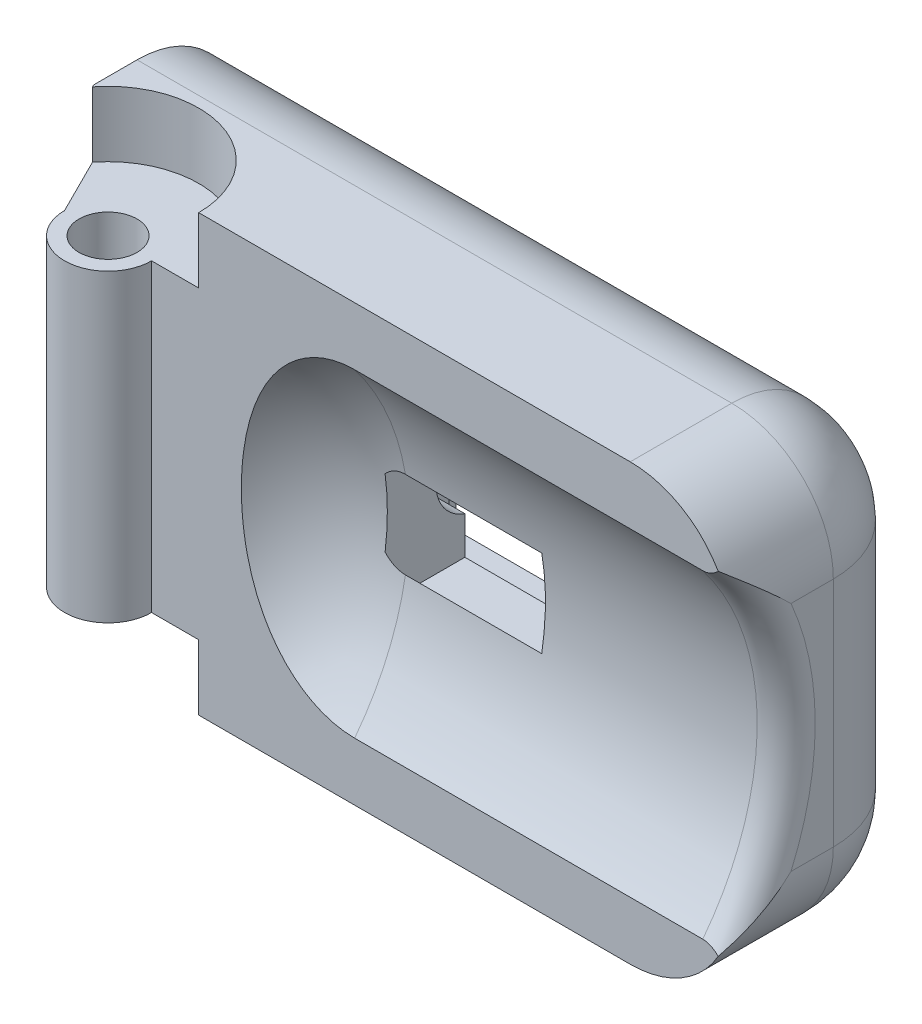
SolidWorks part; units mm, degrees
ref_plane "Alzado" through (0, 0, 0) normal (0, 0, 1) x (1, 0, 0)
ref_plane "Planta" through (0, 0, 0) normal (0, 1, 0) x (1, 0, 0)
ref_plane "Vista lateral" through (0, 0, 0) normal (1, 0, 0) x (0, 0, -1)
sketch "Croquis1" plane through (0, 0, 0) normal (0, 0, 1) x (1, 0, 0)
  line L1 (-43.9768, 15.9874) -> (4.0232, 15.9874)
  line L2 (-43.9768, 15.9874) -> (-43.9768, -14.0126)
  line L3 (-43.9768, -14.0126) -> (4.0232, -14.0126)
  line L4 (4.0232, 15.9874) -> (4.0232, -14.0126)
  dimension "D1" = 48
  dimension "D2" = 30
extrude "Saliente-Extruir1" add sketch "Croquis1" along normal blind 14
sketch "Croquis2" plane through (4.0232, 0, 0) normal (1, 0, 0) x (0, 0, -1)
  line L0 (-14, 15.9874) -> (-14, 11.9874) construction
  line L1 (-14, -14.0126) -> (-14, 15.9874) construction
  line L2 (-14, -14.0126) -> (-14, -10.0126) construction
  line L3 (-14, -14.0126) -> (0, -14.0126) construction
  line L4 (-14, 15.9874) -> (0, 15.9874) construction
  line L5 (-14, 0.9874) -> (-42.4956, 0.9874) construction
  line L6 (-14, 11.9874) -> (-14, -10.0126)
  arc A0 (-14, 11.9874) -> (-14, -10.0126) centre (-28.2478, 0.9874) cw
  line M3 (-14, 15.9874) -> (-14, -14.0126)
  dimension "D1" = 4
  dimension "D2" = 4
extrude "Cortar-Extruir1" cut sketch "Croquis2" against normal blind 36 contours A0 M3 region at (4.0232, 0.9874, 12.4849)
fillet "Redondeo1" radius 2 1 edges at (4.0232, 0.9874, 10.2478)
fillet "Redondeo2" radius 7 5 edges at (-19.9768, -14.0126, 0) (4.0232, 0.9874, 0) (-19.9768, 15.9874, 0) (4.0232, 15.9874, 7) (4.0232, -14.0126, 7)
sketch "Croquis3" plane through (0, 0, 0) normal (0, 0, -1) x (-1, 0, 0)
  line L0 (43.9768, 0.9874) -> (4.1869, 0.9874) construction
  line L2 (43.9768, 8.9874) -> (43.9768, -7.0126) construction
  line L3 (28.9768, -8.0126) -> (28.9768, 9.9874)
  line L4 (28.9768, 9.9874) -> (7.4768, 9.9874)
  line L5 (7.4768, 9.9874) -> (7.4768, -8.0126)
  line L8 (7.4768, -8.0126) -> (28.9768, -8.0126)
  dimension "D1" = 15
  dimension "D2" = 9
  dimension "D3" = 9
  dimension "D4" = 21.5
extrude "Cortar-Extruir2" cut sketch "Croquis3" against normal blind 3
sketch "Croquis5" plane through (0, 0, 0) normal (0, 0, -1) x (-1, 0, 0)
  line L0 (43.9768, 0.9874) -> (24.1183, 0.9874) construction
  line L1 (43.9768, 8.9874) -> (43.9768, -7.0126) construction
  circle A0 centre (17.9768, 0.9874) radius 1
  dimension "D2" = 2
  dimension "D1" = 26
extrude "Cortar-Extruir3" cut sketch "Croquis5" against normal up to surface (10.2478 mm away) up to face at (-14.9768, 0.9874, 12.1239)
sketch "Croquis6" plane through (0, 0, 3) normal (0, 0, -1) x (-1, 0, 0)
  line L0 (17.9768, 0.9874) -> (12.7401, 0.9874) construction
  line L1 (17.9768, 0.9874) -> (17.9768, 7.5082) construction
  line L3 (23.3768, -4.4126) -> (12.5768, -4.4126)
  line L4 (23.3768, -4.4126) -> (23.3768, 6.3874)
  line L5 (23.3768, 6.3874) -> (12.5768, 6.3874)
  line L6 (12.5768, -4.4126) -> (12.5768, 6.3874)
  dimension "D1" = 5.4
  dimension "D2" = 5.4
  dimension "D3" = 5.4
  dimension "D4" = 5.4
extrude "Cortar-Extruir4" cut sketch "Croquis6" against normal blind 7.5
sketch "Croquis7" plane through (0, 0, 3) normal (0, 0, -1) x (-1, 0, 0)
  line L1 (26.4768, 8.9874) -> (26.4768, -7.0126)
  line L2 (17.9768, 6.3874) -> (17.9768, 30.0728) construction
  line L3 (23.3768, 6.3874) -> (12.5768, 6.3874) construction
  line L9 (9.4768, -7.0126) -> (9.4768, 8.9874)
  line L10 (26.4768, -7.0126) -> (9.4768, -7.0126)
  line L12 (9.4768, 8.9874) -> (26.4768, 8.9874)
  point P6 (0, 0)
  point P7 (0, 0)
  point P12 (0, 0)
  point P13 (0, 0)
  dimension "D1" = 8.5
  dimension "D2" = 8.5
extrude "Cortar-Extruir5" cut sketch "Croquis7" against normal blind 2
sketch "Croquis9" plane through (0, -14.0126, 0) normal (0, -1, 0) x (1, 0, 0)
  line L0 (-43.9768, 14) -> (-2.9768, 14) construction
  line L1 (-43.9768, 14) -> (-43.9768, 7) construction
  circle A0 centre (-38.9768, 14) radius 3
  dimension "D1" = 5
extrude "Saliente-Extruir2" add sketch "Croquis9" against normal up to surface (30 mm away) up to face at (-23.4768, 15.9874, 10.5)
sketch "Croquis10" plane through (0, 15.9874, 0) normal (0, 1, 0) x (1, 0, 0)
  circle A0 centre (-38.9768, -14) radius 6.25
extrude "Cortar-Extruir7" cut sketch "Croquis10" against normal blind 4.5
ref_plane "Plano1" through (0, 0.9874, 0) normal (0, 1, 0) x (-1, 0, 0)
mirror "Simetría1" about plane through (0, 0.9874, 0) normal (0, 1, 0) of "Cortar-Extruir7"
sketch "Croquis11" plane through (0, 11.4874, 0) normal (0, 1, 0) x (-1, 0, 0)
  circle A0 centre (38.9768, 14) radius 2
extrude "Cortar-Extruir8" cut sketch "Croquis11" against normal up to surface (21 mm away) up to face at (-39.4565, -9.5126, 13.0391)
sketch "Croquis12" plane through (0, 15.9874, 0) normal (0, 1, 0) x (1, 0, 0)
  line L0 (-43.9768, -14) -> (-41.9768, -14) construction
  line L1 (-43.9768, -10.25) -> (-43.9768, -7) construction
  line L2 (-43.9768, -10) -> (-43.9768, -14) construction
  line L3 (-41.9768, -14) -> (-43.9768, -10) construction
  line L4 (-43.9768, -10) -> (-43.9768, -14)
  line L5 (-43.9768, -14) -> (-41.9768, -14)
  line L6 (-41.9768, -14) -> (-43.9768, -10)
  dimension "D1" = 4
  dimension "D2" = 2
  dimension "D3" = 0
extrude "Cortar-Extruir9" cut sketch "Croquis12" against normal up to surface (30 mm away) up to face at (-25.0565, -14.0126, 9.6391)
sketch "Croquis13" plane through (0, 0, 0) normal (0, 0, -1) x (-1, 0, 0)
  line L0 (43.9768, 0.9874) -> (34.1906, 0.9874) construction
  line L1 (43.9768, 8.9874) -> (43.9768, -7.0126) construction
  line L2 (28.9768, -7.0126) -> (28.9768, 8.9874) construction
  line L3 (28.9768, -1.5126) -> (31.9768, -1.5126)
  line L4 (28.9768, -1.5126) -> (28.9768, 3.4874)
  line L5 (28.9768, 3.4874) -> (31.9768, 3.4874)
  line L6 (31.9768, -1.5126) -> (31.9768, 3.4874)
  dimension "D1" = 5
  dimension "D2" = 3
  dimension "D3" = 2.5
extrude "Cortar-Extruir10" cut sketch "Croquis13" against normal blind 3
fillet "Redondeo3" radius 10 1 edges at (-31.9768, 0.9874, 10.2478)
sketch "Croquis14" plane through (-43.9768, 0, 0) normal (-1, 0, 0) x (0, 0, 1)
  line L0 (0, 8.9874) -> (0, -7.0126) construction
  circle A0 centre (4.0591, 0.9874) radius 2.9486
  point P5 (0, 0)
  point P6 (0, 0)
  point P7 (0, 0.9874)
  dimension "D1" = 4.0591
extrude "Cortar-Extruir15" cut sketch "Croquis14" against normal blind 21
